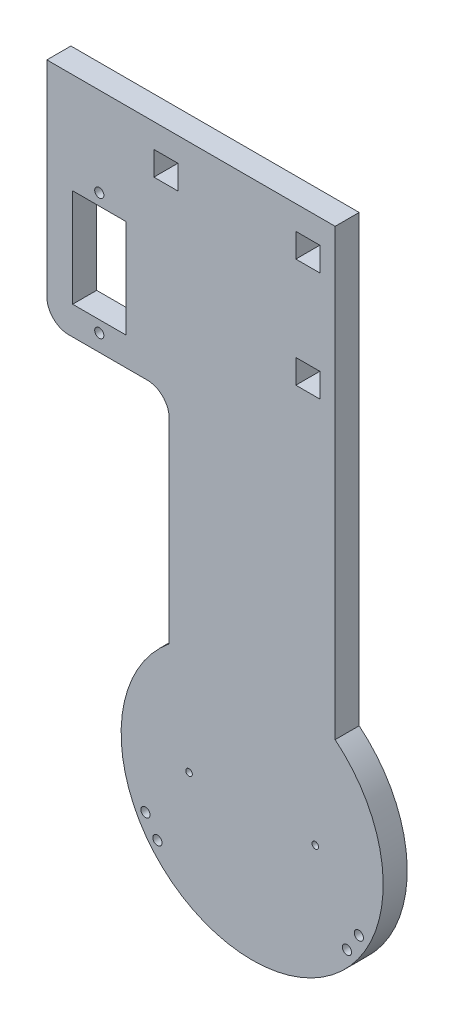
SolidWorks part; units mm, degrees
material "ﾁｰｸ材"
ref_plane "正面" through (0, 0, 0) normal (0, 0, 1) x (1, 0, 0)
ref_plane "平面" through (0, 0, 0) normal (0, 1, 0) x (1, 0, 0)
ref_plane "右側面" through (0, 0, 0) normal (1, 0, 0) x (0, 0, -1)
sketch "ｽｹｯﾁ1" plane through (0, 0, 0) normal (0, 0, 1) x (1, 0, 0)
  line L0 (19, 125) -> (-47, 125)
  line L1 (-19, 73) -> (-19, 23.2164)
  line L2 (19, 125) -> (19, 23.2164)
  line L4 (-47, 125) -> (-47, 73)
  line L6 (-47, 73) -> (-19, 73)
  arc A0 (-19, 23.2164) -> (19, 23.2164) centre (0, 0) ccw
  dimension "D1" = 60
  dimension "D2" = 125
  dimension "D3" = 19
  dimension "D4" = 47
  dimension "D5" = 52
extrude "ﾎﾞｽ - 押し出し1" add sketch "ｽｹｯﾁ1" along normal blind 5.5
sketch "ｽｹｯﾁ2" plane through (0, 0, 5.5) normal (0, 0, 1) x (1, 0, 0)
  line L0 (19, 125) -> (-47, 125) construction
  line L1 (-28.9, 79.5) -> (-41.1, 79.5)
  line L2 (-28.9, 79.5) -> (-28.9, 102)
  line L3 (-28.9, 102) -> (-41.1, 102)
  line L4 (-41.1, 79.5) -> (-41.1, 102)
  line L5 (-28.9, 79.5) -> (-41.1, 102) construction
  line L6 (-28.9, 102) -> (-41.1, 79.5) construction
  point P0 (-35, 90.75)
  dimension "D1" = 12.2
  dimension "D2" = 22.5
  dimension "D3" = 35
  dimension "D4" = 23
extrude "ｶｯﾄ - 押し出し1" cut sketch "ｽｹｯﾁ2" against normal through all
sketch "ｽｹｯﾁ3" plane through (0, 0, 5.5) normal (0, 0, 1) x (1, 0, 0)
  line L0 (0, 0) -> (0, 22.4882) construction
sketch "ｽｹｯﾁ4" plane through (0, 0, 5.5) normal (0, 0, 1) x (1, 0, 0)
  line L0 (19, 125) -> (-47, 125) construction
  line L1 (15.5, 114) -> (10, 114)
  line L2 (15.5, 114) -> (15.5, 119.5)
  line L3 (15.5, 119.5) -> (10, 119.5)
  line L4 (10, 114) -> (10, 119.5)
  line L5 (15.5, 114) -> (10, 119.5) construction
  line L6 (15.5, 119.5) -> (10, 114) construction
  line L7 (0, 0) -> (0, 22.4882) construction
  line L8 (-17, 114) -> (-22.5, 114)
  line L9 (-17, 114) -> (-17, 119.5)
  line L10 (-17, 119.5) -> (-22.5, 119.5)
  line L11 (-22.5, 114) -> (-22.5, 119.5)
  line L12 (-17, 114) -> (-22.5, 119.5) construction
  line L13 (-17, 119.5) -> (-22.5, 114) construction
  line L14 (-28.9, 102) -> (-41.1, 102) construction
  line L15 (15.5, 89) -> (10, 89)
  line L16 (15.5, 89) -> (15.5, 94.5)
  line L17 (15.5, 94.5) -> (10, 94.5)
  line L18 (10, 89) -> (10, 94.5)
  line L19 (15.5, 89) -> (10, 94.5) construction
  line L20 (15.5, 94.5) -> (10, 89) construction
  line L21 (-41.1, 79.5) -> (-28.9, 79.5) construction
  circle A0 centre (-35, 104.65) radius 1.05
  circle A1 centre (-35, 76.85) radius 1.05
  point P0 (12.75, 116.75)
  point P9 (-19.75, 116.75)
  point P14 (12.75, 91.75)
  point P28 (-35, 79.5)
  dimension "D11" = 2.1
  dimension "D1" = 5.5
  dimension "D2" = 5.5
  dimension "D3" = 5.5
  dimension "D4" = 10
  dimension "D5" = 5.5
  dimension "D6" = 5.5
  dimension "D7" = 27
  dimension "D8" = 5.5
  dimension "D9" = 5.5
  dimension "D10" = 25
  dimension "D12" = 2.65
  dimension "D13" = 2.65
extrude "ｶｯﾄ - 押し出し2" cut sketch "ｽｹｯﾁ4" against normal through all
fillet "ﾌｨﾚｯﾄ1" radius 5 1 edges at (-47, 73, 2.75)
fillet "ﾌｨﾚｯﾄ2" radius 5 1 edges at (-19, 73, 2.75)
sketch "ｽｹｯﾁ5" plane through (0, 0, 5.5) normal (0, 0, 1) x (1, 0, 0)
  circle A0 centre (14.45, 0) radius 0.75
  circle A1 centre (-14.45, 0) radius 0.75
  dimension "D1" = 14.45
  dimension "D2" = 1.5
  dimension "D3" = 14.45
extrude "ｶｯﾄ - 押し出し3" cut sketch "ｽｹｯﾁ5" against normal through all
sketch "ｽｹｯﾁ6" plane through (0, 0, 5.5) normal (0, 0, 1) x (1, 0, 0)
  line L0 (0, 0) -> (-25.1601, -16.3392) construction
  line L1 (0, 0) -> (0, 22.4882) construction
  line L2 (-21.7018, -17.0742) -> (-24.425, -12.8809) construction
  line L3 (0, 0) -> (0, -5.9449) construction
  arc A0 (-19, 23.2164) -> (19, 23.2164) centre (0, 0) ccw construction
  circle A1 centre (-24.425, -12.8809) radius 1.05
  circle A2 centre (-21.7018, -17.0742) radius 1.05
  circle A3 centre (24.425, -12.8809) radius 1.05
  circle A4 centre (21.7018, -17.0742) radius 1.05
  point P12 (-23.0634, -14.9776)
  dimension "D2" = 5
  dimension "D3" = 2.1
  dimension "D4" = 2.1
  dimension "D1" = 123
  dimension "D5" = 27.5
extrude "ｶｯﾄ - 押し出し4" cut sketch "ｽｹｯﾁ6" against normal through all
